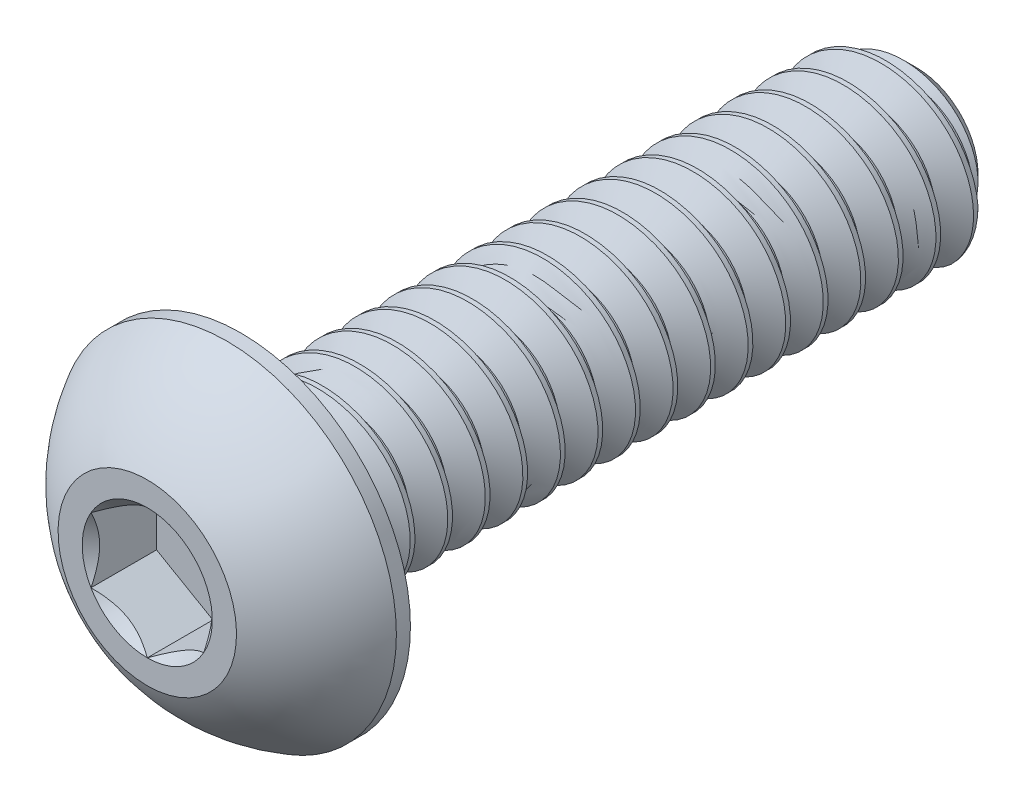
SolidWorks part; units mm, degrees
ref_plane "Front" through (0, 0, 0) normal (0, 0, 1) x (1, 0, 0)
ref_plane "Top" through (0, 0, 0) normal (0, 1, 0) x (1, 0, 0)
ref_plane "Right" through (0, 0, 0) normal (1, 0, 0) x (0, 0, -1)
sketch "Sketch1" plane through (0, 0, 0) normal (1, 0, 0) x (0, 0, -1)
  line L2 (1.3208, 1.2573) -> (10.8458, 1.2573)
  line L3 (10.8458, 1.2573) -> (10.8458, 0)
  line L4 (10.8458, 0) -> (1.3208, 0)
  line L6 (1.1227, 2.3876) -> (1.3208, 2.3876) construction
  line L7 (10.8458, 1.2573) -> (10.8458, -1.2573) construction
  line L8 (0, 0) -> (1.3208, 0) construction
  line L9 (1.3208, 2.3876) -> (1.3208, -2.3876) construction
  line L11 (1.3208, 1.2573) -> (1.3208, 0)
  line L13 (0, 0.7937) -> (0, -0.7937) construction
  line L14 (0, 0.7937) -> (0, 1.2573) construction
  arc A3 (0, 1.2573) -> (1.1227, 2.3876) centre (2.3962, 0) cw construction
  dimension "D1" = 0.1981
revolve "Revolve1" add sketch "Sketch1" angle 360 mid plane about L4
sketch "Sketch3" plane through (0, 0, -10.8458) normal (0, 0, -1) x (-1, 0, 0)
  circle A0 centre (0, 0) radius 1.2573
curve "Helix/Spiral1" pitch 0.5292 height 10.0542 radius 1.2573 centre (0, 0, -10.8458) axis (0, 0, 1) start towards (0, 1, 0)
sketch "Sketch2" plane through (0, 0, 0) normal (1, 0, 0) x (0, 0, -1)
  line L0 (10.8458, 1.2573) -> (11.3088, 1.2573)
  line L1 (11.3088, 1.2573) -> (11.1104, 0.9136)
  line L2 (11.1104, 0.9136) -> (11.0442, 0.9136)
  line L3 (11.0442, 0.9136) -> (10.8458, 1.2573)
  line L4 (10.945, 1.0854) -> (11.2096, 1.0854) construction
  dimension "D1" = 60
  dimension "D2" = 0.0661
  dimension "D3" = 0.2646
chamfer "Chamfer1" distance 0.3969 angle 45 1 edges at (0, 1.2573, -10.8458)
sweep "Cut-Sweep1" cut profiles "Sketch2" path "Helix/Spiral1" align with end faces yes
sketch "Sketch7" plane through (0, 0, 0) normal (1, 0, 0) x (0, 0, -1)
  line L6 (1.1227, 2.3876) -> (1.3208, 2.3876) construction
  line L8 (0, 0) -> (1.3208, 0) construction
  line L11 (1.3208, 2.3876) -> (1.3208, -2.3876) construction
  line L12 (1.1227, 2.3876) -> (1.3208, 2.3876)
  line L13 (0, 0) -> (1.3208, 0)
  line L14 (0, 0.7937) -> (0, -0.7937) construction
  line L15 (1.3208, 2.3876) -> (1.3208, 0)
  line L16 (0, 1.2573) -> (0, 0)
  arc A2 (1.1227, 2.3876) -> (0, 1.2573) centre (2.3962, 0) ccw construction
  arc A3 (1.1227, 2.3876) -> (0, 1.2573) centre (2.3962, 0) ccw
revolve "Revolve2" add sketch "Sketch7" angle 360 mid plane about L13
sketch "Sketch5" plane through (0, 0, 0) normal (0, 0, 1) x (1, 0, 0)
  line L1 (0.7937, -0.4583) -> (0.7937, 0.4583)
  line L2 (0.7937, 0.4583) -> (0, 0.9165)
  line L3 (0, 0.9165) -> (-0.7937, 0.4583)
  line L4 (-0.7937, 0.4583) -> (-0.7937, -0.4583)
  line L5 (-0.7937, -0.4583) -> (0, -0.9165)
  line L6 (0, -0.9165) -> (0.7937, -0.4583)
  circle A0 centre (0, 0) radius 0.7937 construction
extrude "Cut-Extrude2" cut sketch "Sketch5" against normal blind 0.9246
sketch "Sketch6" plane through (0, 0, 0) normal (0, 0, 1) x (1, 0, 0)
  circle A0 centre (0, 0) radius 0.9165
extrude "Cut-Extrude3" cut sketch "Sketch6" against normal blind 0.9246 draft 45
sketch "Sketch9" [suppressed] plane through (0, 0, -1.4986) normal (0, 0, 1) x (1, 0, 0)
  circle A2 centre (0, 0) radius 1.4224
extrude "Boss-Extrude2" [suppressed] add sketch "Sketch9" against normal offset from surface (12.7 mm away) 31.75 up to face at (0, 0.8604, -10.8458)
sketch "Sketch10" plane through (0, 0, 0) normal (1, 0, 0) x (0, 0, -1)
  line L0 (10.8458, 1.2573) -> (10.8458, -1.2573) construction
  point P0 (10.052, -1.2573)
  dimension "D1" = 0.7937
equation "\"D3@Helix/Spiral1\" = \"Lg@Sketch1\" + \"D4@Helix/Spiral1\""
equation "\"D2@Sketch2\" = \"D4@Helix/Spiral1\" * .125"
equation "\"D3@Sketch2\" = \"D4@Helix/Spiral1\" * .5"
equation "\"D1@Chamfer1\" = \"D4@Helix/Spiral1\" * .75"
equation "\"D1@Cut-Extrude2\" = \"Head Ht@Sketch1\" * .7"
equation "\"D1@Sketch1\" = \"Head Ht@Sketch1\" * .15"
equation "\"D1@Sketch10\" = \"D4@Helix/Spiral1\" * 1.5"
equation "\"D1@Cut-Extrude3\" = \"D1@Cut-Extrude2\""
